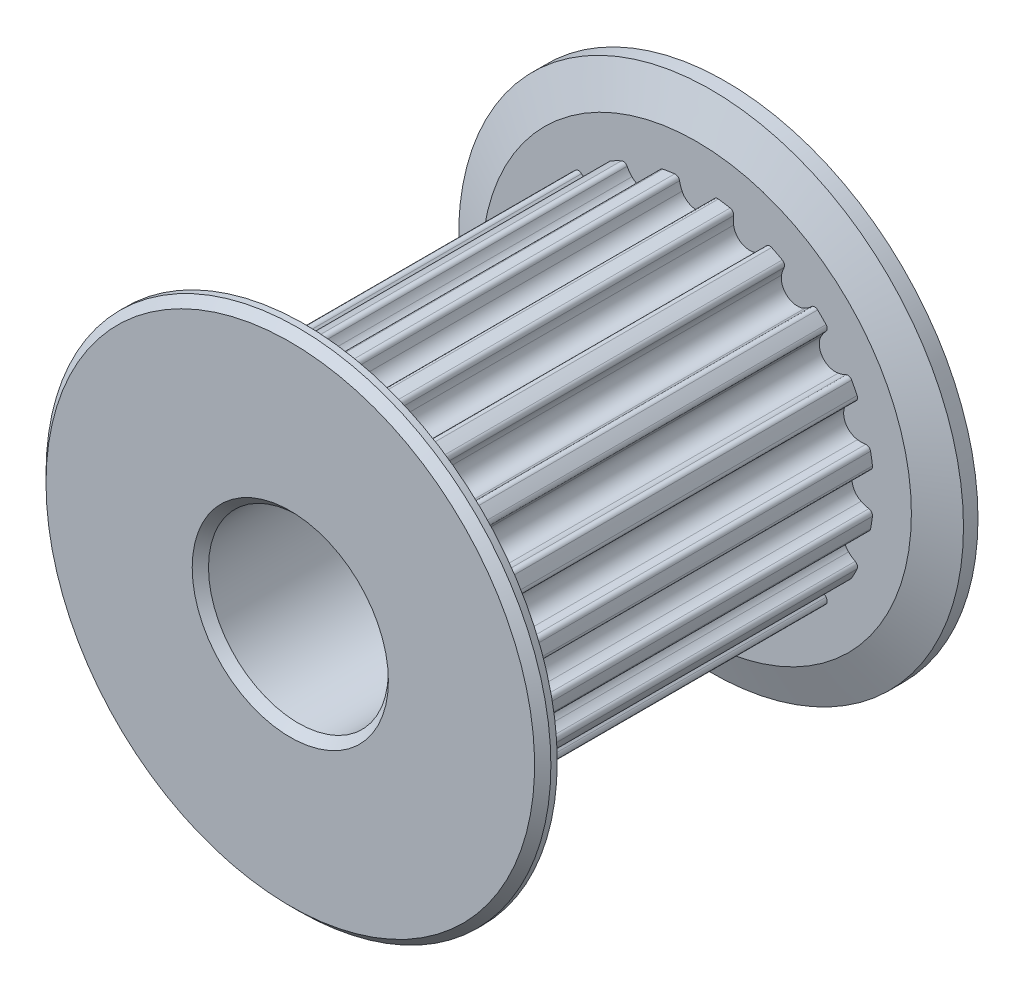
SolidWorks part; units mm, degrees
ref_plane "Front Plane" through (0, 0, 0) normal (0, 0, 1) x (1, 0, 0)
ref_plane "Top Plane" through (0, 0, 0) normal (0, 1, 0) x (1, 0, 0)
ref_plane "Right Plane" through (0, 0, 0) normal (1, 0, 0) x (0, 0, -1)
sketch "Sketch1" plane through (0, 0, 0) normal (0, 0, 1) x (1, 0, 0)
  line L1 (-1.7499, 5.3585) -> (1.7499, 5.3585) construction
  line L4 (0, 0) -> (0, 5.3585) construction
  line L5 (0, 5.3585) -> (0, 11.2107) construction
  line L6 (0, 6.3625) -> (1.9751, 6.0482) construction
  line L7 (1.9751, 6.0482) -> (2.6648, 5.8229) construction
  line L8 (1.9751, 6.0482) -> (1.7499, 5.3585) construction
  line L9 (-1.9751, 6.0482) -> (-1.7499, 5.3585) construction
  line L10 (-1.8963, 5.8067) -> (-2.841, 8.6995)
  line L11 (-2.841, 8.6995) -> (2.841, 8.6995)
  line L12 (2.841, 8.6995) -> (1.8963, 5.8067)
  circle A0 centre (0, 0) radius 6.3625 construction
  circle A1 centre (0, 0) radius 8.6995 construction
  circle A2 centre (0, 0) radius 6.1085 construction
  arc A3 (-0.4989, 5.6703) -> (0.4989, 5.6703) centre (0, 5.9135) ccw
  arc A4 (-0.4989, 5.6703) -> (-0.5855, 5.9387) centre (0.4, 6.1085) cw
  arc A5 (-1.8963, 5.8067) -> (-0.7518, 6.0621) centre (0, 0) cw
  arc A6 (-0.5855, 5.9387) -> (-0.7518, 6.0621) centre (-0.7333, 5.9132) ccw
  arc A7 (1.8963, 5.8067) -> (0.7518, 6.0621) centre (0, 0) ccw
  arc A8 (0.5855, 5.9387) -> (0.7518, 6.0621) centre (0.7333, 5.9132) cw
  arc A9 (0.4989, 5.6703) -> (0.5855, 5.9387) centre (-0.4, 6.1085) ccw
  point P6 (0, 20.9083)
  point P11 (0, 6.3625)
  point P13 (0, 8.6995)
  point P14 (0, 6.1085)
  dimension "D1" = 9.6976
  dimension "PD" = 12.725
  dimension "D2" = 4.8482
  dimension "OD" = 17.399
  dimension "R3" = 0.555
  dimension "R2" = 1
  dimension "R1" = 0.15
  dimension "b" = 0.4
  dimension "D3" = 2
  dimension "PLD" = 0.254
  dimension "h" = 0.75
sketch "Sketch2" plane through (0, 0, 0) normal (1, 0, 0) x (0, 0, -1)
  line L0 (-7.5, 3.1) -> (7.5, 3.1)
  line L1 (-7.5, 3.1) -> (-7.5, 8.6995)
  line L2 (-7, 8.6995) -> (-7.5, 8.6995)
  line L3 (-7.5, 3.1) -> (-7.5, 8.6995) construction
  line L4 (-7.5, 8.6995) -> (-6.5, 8.6995) construction
  line L5 (-6.5, 8.6995) -> (-6.5, 6.1085) construction
  line L6 (-6.5, 6.1085) -> (6.5, 6.1085)
  line L7 (6.5, 6.1085) -> (6.5, 8.6995) construction
  line L8 (6.5, 8.6995) -> (7.5, 8.6995) construction
  line L9 (7.5, 8.6995) -> (7.5, 3.1)
  line L10 (-7.5, 0) -> (7.5, 0) construction
  line L11 (7, 8.6995) -> (6.5, 7.404)
  line L12 (-6.5, 7.404) -> (-7, 8.6995)
  line L14 (-6.5, 7.404) -> (-6.5, 6.1085)
  line L15 (6.5, 6.1085) -> (6.5, 7.404)
  line L16 (7, 8.6995) -> (7.5, 8.6995)
  arc A0 (-6.5, 7.404) -> (-7, 8.6995) centre (-8.4283, 7.404) ccw construction
  arc A1 (6.5, 7.404) -> (7, 8.6995) centre (8.4283, 7.404) cw construction
  point P12 (-6.5, 7.404)
  point P14 (-7, 8.6995)
  point P20 (6.5, 7.404)
  point P21 (7, 8.6995)
  point P25 (6.5, 0)
  point P26 (-6.5, 0)
  dimension "OA" = 15
  dimension "Bore" = 6.2
  dimension "Outside Width" = 14
  dimension "Inside Width" = 13
revolve "Revolve1" add sketch "Sketch2" angle 360 mid plane about L10
sketch "Sketch3" plane through (0, 0, 0) normal (0, 0, 1) x (1, 0, 0)
  line L6 (2.841, 8.6995) -> (-2.841, 8.6995)
  line L7 (1.8963, 5.8067) -> (2.841, 8.6995)
  line L8 (-2.841, 8.6995) -> (-1.8963, 5.8067)
  line L9 (2.841, 8.6995) -> (-2.841, 8.6995)
  line L10 (1.8963, 5.8067) -> (2.841, 8.6995)
  line L11 (-2.841, 8.6995) -> (-1.8963, 5.8067)
  arc A8 (1.8963, 5.8067) -> (0.7518, 6.0621) centre (0, 0) ccw
  arc A9 (0.7518, 6.0621) -> (0.5855, 5.9387) centre (0.7333, 5.9132) ccw
  arc A10 (0.4989, 5.6703) -> (0.5855, 5.9387) centre (-0.4, 6.1085) ccw
  arc A11 (-0.4989, 5.6703) -> (0.4989, 5.6703) centre (0, 5.9135) ccw
  arc A12 (-0.5855, 5.9387) -> (-0.4989, 5.6703) centre (0.4, 6.1085) ccw
  arc A13 (-0.5855, 5.9387) -> (-0.7518, 6.0621) centre (-0.7333, 5.9132) ccw
  arc A14 (-0.7518, 6.0621) -> (-1.8963, 5.8067) centre (0, 0) ccw
  arc A15 (1.8963, 5.8067) -> (0.7518, 6.0621) centre (0, 0) ccw
  arc A16 (0.7518, 6.0621) -> (0.5855, 5.9387) centre (0.7333, 5.9132) ccw
  arc A17 (0.4989, 5.6703) -> (0.5855, 5.9387) centre (-0.4, 6.1085) ccw
  arc A18 (-0.4989, 5.6703) -> (0.4989, 5.6703) centre (0, 5.9135) ccw
  arc A19 (-0.5855, 5.9387) -> (-0.4989, 5.6703) centre (0.4, 6.1085) ccw
  arc A20 (-0.5855, 5.9387) -> (-0.7518, 6.0621) centre (-0.7333, 5.9132) ccw
  arc A21 (-0.7518, 6.0621) -> (-1.8963, 5.8067) centre (0, 0) ccw
  dimension "D1" = 0
extrude "Cut-Extrude1" cut sketch "Sketch3" against normal up to vertex (6.5 mm away) from vertex up to point (0, 6.1085, -6.5) starting at point (0, 6.1085, 6.5)
pattern_circular "CirPattern1" count 20 over 360 about axis through (0, 0, 7.5) along (0, 0, 1) of "Cut-Extrude1"
sketch "Sketch4" plane through (0, 0, 0) normal (1, 0, 0) x (0, -1, 0)
  line L0 (0, -6.5) -> (0, -7.5) construction
  line L1 (-3.1, -7.5) -> (3.1, -7.5) construction
  line L2 (7.404, -6.5) -> (-7.404, -6.5) construction
  circle A0 centre (0, -7) radius 1.7526
  dimension "Set Screw" = 3.5052
ref_plane "Plane1" through (0, 0, 7) normal (0, 0, 1) x (1, 0, 0)
chamfer "Chamfer1" distance 0.2807 angle 45 2 edges at (3.1, 0, 7.5) (8.6995, 0, 7.5)
ref_axis "Center Axis 1" through (0, 0, -7.5) along (0, 0, 1)
ref_plane "Contact Plane 1" through (0, 0, 7.5) normal (0, 0, 1) x (1, 0, 0)
ref_plane "Contact Plane 2" through (0, 0, -7.5) normal (0, 0, -1) x (-1, 0, 0)
sketch "Sketch5" plane through (0, 0, -7.5) normal (0, 0, -1) x (-1, 0, 0)
  line L0 (-1.6882, -2.6) -> (1.6882, -2.6)
  line L1 (-1.6882, -2.6) -> (-1.6882, -3.1)
  line L2 (-1.6882, -3.1) -> (1.6882, -3.1)
  line L3 (1.6882, -3.1) -> (1.6882, -2.6)
  circle A0 centre (0, 0) radius 3.1 construction
  dimension "D1" = 2.6
  dimension "D2" = 0.5
extrude "Boss-Extrude1" add sketch "Sketch5" against normal blind 9
